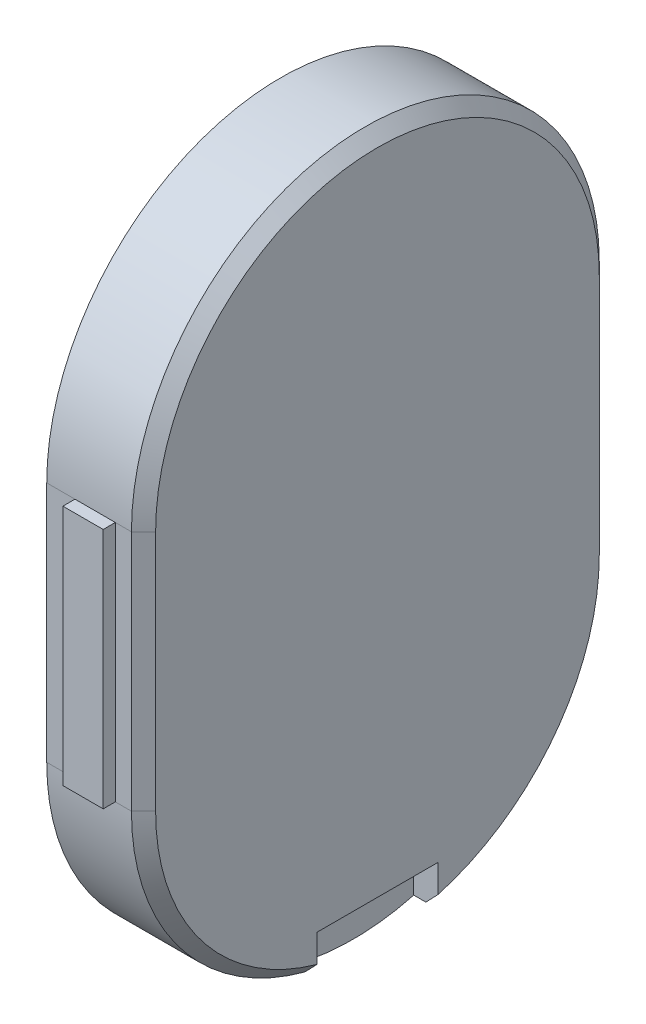
SolidWorks part; units mm, degrees
ref_plane "Front Plane" through (0, 0, 0) normal (0, 0, 1) x (1, 0, 0)
ref_plane "Top Plane" through (0, 0, 0) normal (0, 1, 0) x (1, 0, 0)
ref_plane "Right Plane" through (0, 0, 0) normal (1, 0, 0) x (0, 0, -1)
sketch "Sketch1" plane through (0, 0, 0) normal (1, 0, 0) x (0, 0, -1)
  line L0 (-73.2, 110) -> (-73.2, 116)
  line L1 (-61.6, 116) -> (-61.6, 110)
  arc A0 (-61.6, 110) -> (-67.4, 104.2) centre (-67.4, 110) cw
  arc A1 (-67.4, 104.2) -> (-73.2, 110) centre (-67.4, 110) cw
  arc A2 (-73.2, 116) -> (-67.4, 121.8) centre (-67.4, 116) cw
  arc A3 (-67.4, 121.8) -> (-61.6, 116) centre (-67.4, 116) cw
extrude "Boss-Extrude1" add sketch "Sketch1" along normal blind 2.4 from offset 60.6
chamfer "Chamfer1" distance 0.3 angle 45 4 edges at (63, 104.2, 67.4) (63, 113, 61.6) (63, 113, 73.2) (63, 121.8, 67.4)
sketch "Sketch2" plane through (0, 0, 0) normal (0, 0, 1) x (1, 0, 0)
  line L1 (61.3, 110) -> (62.3, 110)
  line L2 (61.3, 110) -> (61.3, 116)
  line L3 (61.3, 116) -> (62.3, 116)
  line L4 (62.3, 110) -> (62.3, 116)
extrude "Boss-Extrude2" add sketch "Sketch2" along normal blind 0.31 from offset 61.3
sketch "Sketch3" plane through (0, 0, 0) normal (0, 0, 1) x (1, 0, 0)
  line L1 (61.3, 110) -> (62.3, 110)
  line L2 (61.3, 110) -> (61.3, 116)
  line L3 (61.3, 116) -> (62.3, 116)
  line L4 (62.3, 110) -> (62.3, 116)
extrude "Boss-Extrude3" add sketch "Sketch3" along normal blind 0.31 from offset 73.19
sketch "Sketch4" plane through (0, 0, 0) normal (0, 0, 1) x (1, 0, 0)
  line L1 (62.4, 104.1) -> (63.1, 104.1)
  line L2 (62.4, 104.1) -> (62.4, 105.4)
  line L3 (62.4, 105.4) -> (63.1, 105.4)
  line L4 (63.1, 104.1) -> (63.1, 105.4)
extrude "Boss-Extrude4" add sketch "Sketch4" along normal blind 3 from offset 65.9 separate body
combine bodies "Combine1" operation type subtract main body 103 bodies to subtract 104
